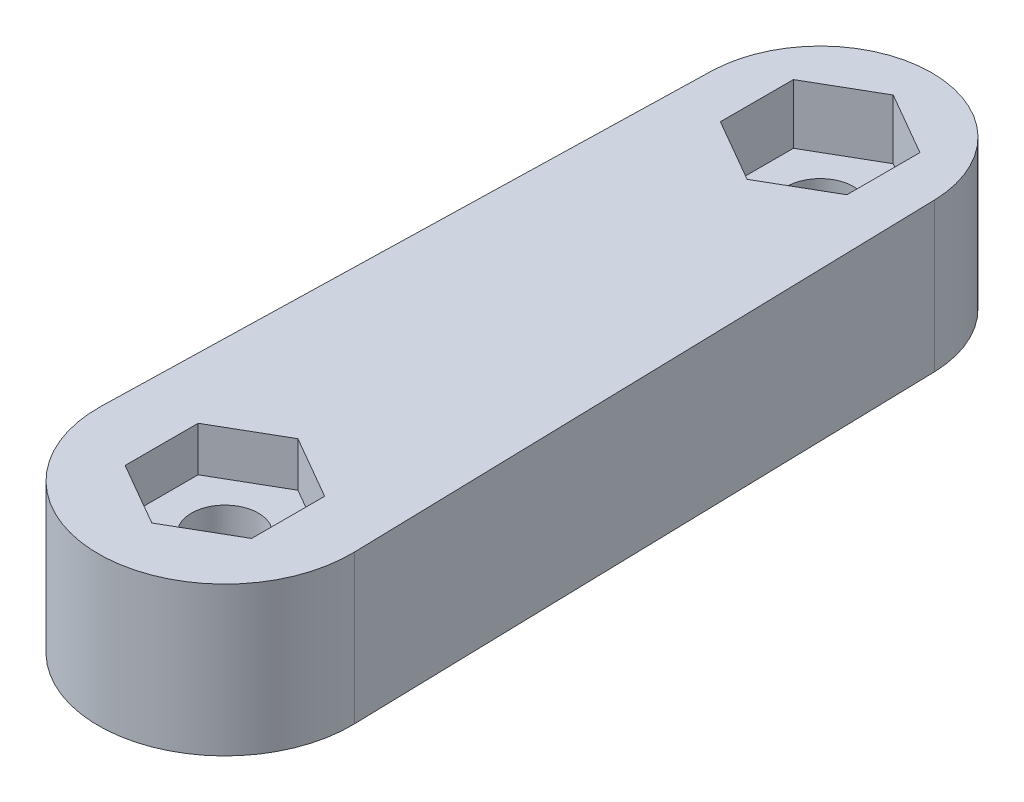
SolidWorks part; units mm, degrees
ref_plane "Front Plane" through (0, 0, 0) normal (0, 0, 1) x (1, 0, 0)
ref_plane "Top Plane" through (0, 0, 0) normal (0, 1, 0) x (1, 0, 0)
ref_plane "Right Plane" through (0, 0, 0) normal (1, 0, 0) x (0, 0, -1)
sketch "Sketch1" plane through (0, 0, 0) normal (0, 1, 0) x (1, 0, 0)
  line L0 (0, 0) -> (0, 20) construction
  line L1 (-4.2487, 0.1063) -> (-3.7488, 20.0938)
  line L2 (4.2487, 0.1063) -> (3.7488, 20.0938)
  circle A0 centre (0, 20) radius 3.75
  circle A1 centre (0, 0) radius 4.25
  circle A2 centre (0, 20) radius 1.125
  circle A3 centre (0, 0) radius 1.125
  dimension "D1" = 7.5
  dimension "D2" = 8.5
  dimension "D4" = 2.25
  dimension "D5" = 2.25
  dimension "D3" = 20
extrude "Boss-Extrude1" add sketch "Sketch1" along normal blind 5 contours L0 A1 L2 A0 | A1 L0 A0 L1 | A3 A1 | A0 A2 region at (2.8835, 0, -2.9565) region at (-2.1379, 0, -10.1229) region at (2.1379, 0, -10.1229) region at (-2.6087, 0, -17.4558)
sketch "Sketch2" plane through (0, 0, 0) normal (0, 1, 0) x (1, 0, 0)
  line L0 (2.85, 0) -> (2.85, 15)
  line L5 (2.225, 0) -> (2.225, 15)
  line L6 (2.225, 15) -> (2.85, 15)
  circle A0 centre (0, 0) radius 2.85
  circle M22 centre (0, 0) radius 1.125
  dimension "D1" = 5.7
  dimension "D2" = 15
  dimension "D3" = 0.625
extrude "Cut-Extrude1" cut sketch "Sketch2" along normal blind 2 contours A0 M22 | L0 A0 L5 L6
sketch "Sketch3" plane through (0, 0, 0) normal (0, -1, 0) x (1, 0, 0)
  line L0 (0, 0) -> (0, -20) construction
  line L7 (0, -10) -> (6.9077, -10) construction
  line L22 (2.125, -21.2269) -> (0, -22.4537)
  line L23 (0, 2.4537) -> (-2.125, 1.2269)
  line L24 (-2.125, 1.2269) -> (-2.125, -1.2269)
  line L25 (-2.125, -1.2269) -> (0, -2.4537)
  line L26 (0, -2.4537) -> (2.125, -1.2269)
  line L27 (2.125, -1.2269) -> (2.125, 1.2269)
  line L28 (2.125, 1.2269) -> (0, 2.4537)
  line L29 (2.125, -18.7731) -> (2.125, -21.2269)
  line L30 (0, -17.5463) -> (2.125, -18.7731)
  line L31 (-2.125, -18.7731) -> (0, -17.5463)
  line L32 (-2.125, -21.2269) -> (-2.125, -18.7731)
  line L33 (0, -22.4537) -> (-2.125, -21.2269)
  circle A1 centre (0, 0) radius 2.125 construction
  circle A4 centre (0, -20) radius 2.125 construction
  dimension "D1" = 4.25
extrude "Cut-Extrude2" cut sketch "Sketch3" along normal blind 1.5 from surface contours L27 L24 L25 L26 region at (0, 0, 0) starting at face at (0, 5, -9.925)
extrude "Cut-Extrude3" cut sketch "Sketch3<3>" along normal blind 2 from surface contours L31 L30 L29 L22 L33 L32 starting at face at (0, 5, 0)
sketch "Sketch3<3>" plane through (0, 0, 0) normal (0, -1, 0) x (1, 0, 0) same geometry as "Sketch3"
